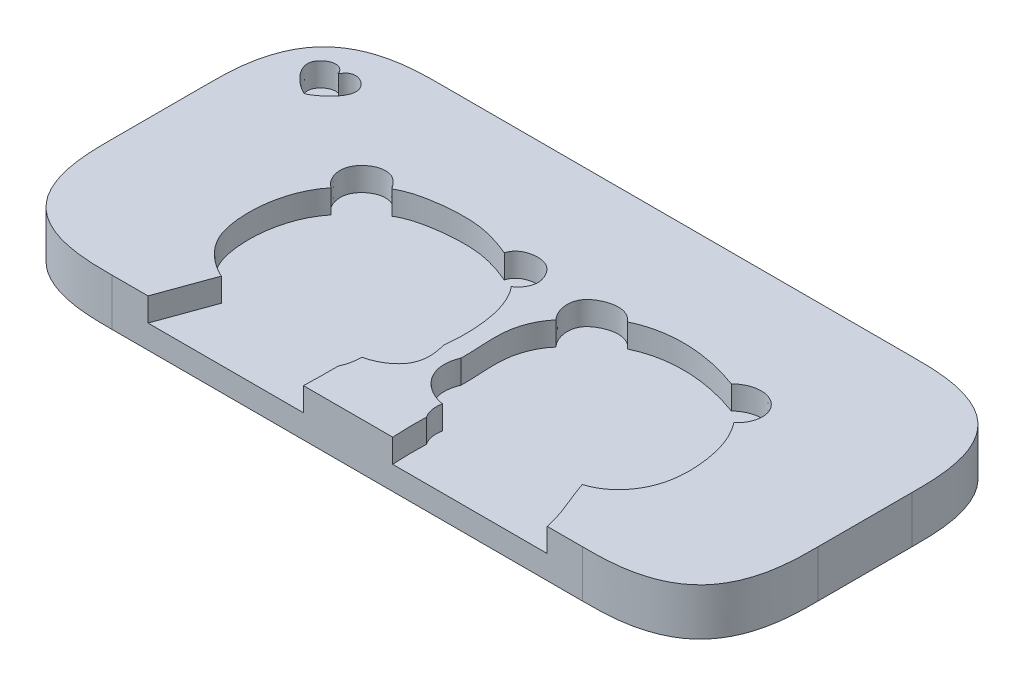
SolidWorks part; units mm, degrees
ref_plane "前视基准面" through (0, 0, 0) normal (0, 0, 1) x (1, 0, 0)
ref_plane "上视基准面" through (0, 0, 0) normal (0, 1, 0) x (1, 0, 0)
ref_plane "右视基准面" through (0, 0, 0) normal (1, 0, 0) x (0, 0, -1)
other "Configuration Table"
sketch "草图1" plane through (0, 0, 0) normal (0, 1, 0) x (1, 0, 0)
  line L1 (-30, 14) -> (30, 14)
  line L2 (-30, 14) -> (-30, -14)
  line L3 (-30, -14) -> (30, -14)
  line L4 (30, 14) -> (30, -14)
  line L5 (-30, 14) -> (30, -14) construction
  line L6 (-30, -14) -> (30, 14) construction
  point P0 (0, 0)
  dimension "D1" = 60
  dimension "D2" = 28
extrude "凸台-拉伸1" add sketch "草图1" along normal blind 4
fillet "圆角1" radius 10 4 edges at (30, 2, 14) (30, 2, -14) (-30, 2, -14) (-30, 2, 14) curvature continuous yes
sketch "草图2" plane through (0, 4, 0) normal (0, 1, 0) x (1, 0, 0)
  line L0 (0, 0) -> (0, 14) construction
  line L1 (20, 14) -> (-20, 14) construction
  line L2 (0, 14) -> (0, -14) construction
  line L3 (-20, -14) -> (20, -14) construction
  line L4 (141.7529, 248.4196) -> (754.4195, 248.4196) construction
  line L5 (-16.9351, -14) -> (-3.7249, -14)
  line L6 (3.8595, -14) -> (16.9895, -14)
  line L7 (-25.185, 10.4317) -> (-25.185, 7.5318) construction
  spline S0 degree 1 poles (-16.9351, -14) (-15.2803, -9.4293) knots 0 0 1 1
  spline S1 degree 3 poles (-15.2803, -9.4293) (-16.4977, -8.8663) (-18.2942, -7.3469) (-18.8729, -4.3152) (-18.7457, -1.369) (-17.9441, 0.7286) (-17.1124, 1.7402) knots 0 0 0 0 0.318174 0.494605 0.698393 1 1 1 1
  spline S2 degree 3 poles (-17.1124, 1.7402) (-17.7969, 2.1592) (-18.3612, 3.5965) (-17.3569, 4.8812) (-16.403, 5.37) (-15.2083, 5.2561) (-14.6852, 4.5877) (-14.4436, 4.2258) knots 0 0 0 0 0.353241 0.517927 0.663977 0.804852 1 1 1 1
  spline S3 degree 3 poles (-14.4436, 4.2258) (-13.6618, 4.702) (-12.0796, 5.0886) (-9.8087, 5.3255) (-7.4385, 5.2358) (-5.8595, 4.6837) (-4.9638, 4.31) knots 0 0 0 0 0.277672 0.49398 0.700925 1 1 1 1
  spline S4 degree 3 poles (-4.9638, 4.31) (-4.793, 4.9772) (-3.7528, 5.5327) (-2.2782, 5.3413) (-1.5316, 4.4657) (-1.1488, 3.2423) (-1.7435, 2.3899) (-2.1871, 2.1223) knots 0 0 0 0 0.278653 0.467418 0.607717 0.765484 1 1 1 1
  spline S5 degree 3 poles (-2.1871, 2.1223) (-1.4106, 1.2046) (-0.5925, -1.244) (-0.6007, -3.7916) (-0.7427, -5.1278) knots 0 0 0 0 0.466812 1 1 1 1
  spline S6 degree 3 poles (-0.7427, -5.1278) (-0.5192, -5.8803) (-0.2929, -8.0506) (-2.3414, -9.2203) (-3.3333, -9.4293) knots 0 0 0 0 0.428917 1 1 1 1
  spline S7 degree 2 poles (-3.3333, -9.4293) (-3.3308, -10.3027) (-3.6878, -11.1002) knots 0 0 0 1 1 1
  spline S8 degree 2 poles (-3.6878, -11.1002) (-3.6708, -12.5507) (-3.7249, -14) knots 0 0 0 1 1 1
  spline S9 degree 2 poles (3.8595, -14) (3.7696, -12.5503) (3.822, -11.1002) knots 0 0 0 1 1 1
  spline S10 degree 2 poles (3.822, -11.1002) (3.3379, -10.3447) (3.5244, -9.4293) knots 0 0 0 1 1 1
  spline S11 degree 3 poles (3.5244, -9.4293) (2.558, -9.2829) (1.1923, -8.4515) (0.5739, -6.6019) (0.7592, -5.696) (0.9415, -5.2622) knots 0 0 0 0 0.526962 0.748178 1 1 1 1
  spline S12 degree 3 poles (0.9415, -5.2622) (0.9857, -3.8874) (0.5232, -1.4667) (1.5212, 0.8304) (2.1708, 1.5742) knots 0 0 0 0 0.583806 1 1 1 1
  spline S13 degree 3 poles (2.1708, 1.5742) (1.5811, 2.1329) (1.1385, 3.8787) (3.1694, 5.3179) (4.665, 5.2833) (5.3599, 4.4642) knots 0 0 0 0 0.379311 0.599175 1 1 1 1
  spline S14 degree 3 poles (5.3599, 4.4642) (8.1477, 5.8222) (11.5377, 5.3546) (14.3332, 4.31) knots 0 0 0 0 1 1 1 1
  spline S15 degree 3 poles (14.3332, 4.31) (14.8136, 4.8053) (15.9197, 5.2736) (17.4232, 4.7837) (18.3931, 3.3773) (17.8865, 2.048) (17.2887, 1.5742) knots 0 0 0 0 0.3053 0.480891 0.659707 1 1 1 1
  spline S16 degree 3 poles (17.2887, 1.5742) (18.2873, 0.3055) (19.0819, -2.3634) (18.8996, -6.7665) (16.921, -8.9861) (15.4049, -9.4293) knots 0 0 0 0 0.370985 0.640432 1 1 1 1
  spline S17 degree 3 poles (15.4049, -9.4293) (15.9004, -10.9602) (16.6938, -12.4075) (16.9895, -14) knots 0 0 0 0 1 1 1 1
  spline S18 degree 3 poles (-25.185, 10.4317) (-25.6893, 11.5573) (-28.7706, 10.0404) (-25.8189, 7.7484) (-25.185, 7.5318) knots 0 0 0 0 0.419336 1 1 1 1
  spline S19 degree 3 poles (-25.185, 10.4317) (-24.6807, 11.5573) (-21.5994, 10.0404) (-24.5512, 7.7484) (-25.185, 7.5318) knots 0 0 0 0 0.419336 1 1 1 1
extrude "切除-拉伸1" cut sketch "草图2" against normal blind 2
